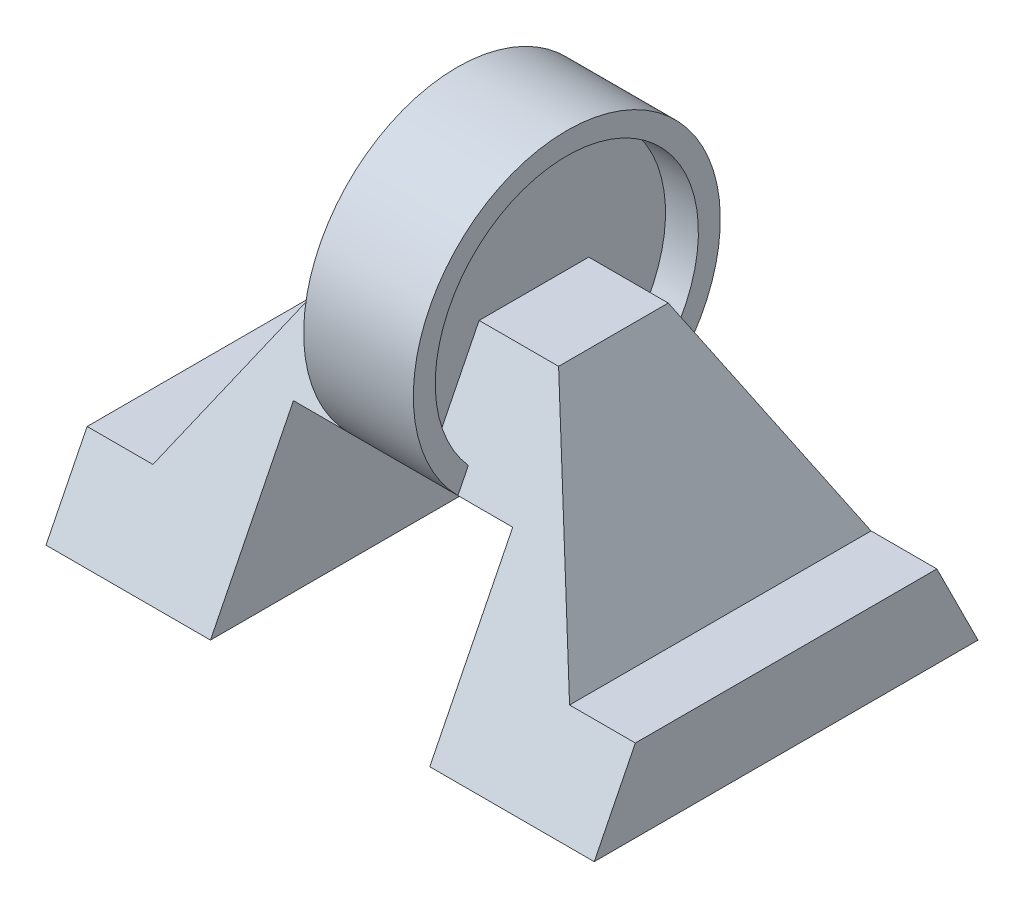
SolidWorks part; units mm, degrees
ref_plane "Front Plane" through (0, 0, 0) normal (0, 0, 1) x (1, 0, 0)
ref_plane "Top Plane" through (0, 0, 0) normal (0, 1, 0) x (1, 0, 0)
ref_plane "Right Plane" through (0, 0, 0) normal (1, 0, 0) x (0, 0, -1)
sketch "Sketch2" plane through (0, 0, 0) normal (1, 0, 0) x (0, 0, -1)
  line L0 (-35, 0) -> (35, 0)
  line L1 (35, 0) -> (10, 50)
  line L2 (10, 50) -> (-10, 50)
  line L3 (-10, 50) -> (-35, 0)
  line L4 (0, 0) -> (0, 29.4444) construction
  line L5 (-19.8659, 30.2682) -> (19.8659, 30.2682)
  arc A0 (-19.8659, 30.2682) -> (19.8659, 30.2682) centre (0, 50) cw
  arc A1 (-13.6622, 30.2682) -> (13.6622, 30.2682) centre (0, 50) cw
  point P4 (0, 0)
  point P12 (0, 0)
  point P14 (0, 0)
  dimension "D4" = 28
  dimension "D5" = 24
  dimension "D1" = 20
  dimension "D2" = 70
  dimension "D3" = 50
extrude "Boss-Extrude1" add sketch "Sketch2" along normal mid plane 100 contours L0 L4 L5 L3 | L4 L0 L1 L5 | L4 L5 A1 L1 L2 | L1 A1 L5 | L5 A1 L3 | L5 L4 L2 L3 A1 region at (0, 14.793, 26.7508) region at (0, 31.5043, 17.24) region at (0, 39.3448, 0) region at (0, 31.5043, -17.24)
extrude "Boss-Extrude2" add sketch "Sketch2<5>" along normal mid plane 20 contours L4 A1 L1 A0 | A1 L4 A0 L3 | L5 A1 L3 | L1 A1 L5 region at (0, 77.2642, 0) region at (0, 31.5043, 17.24) region at (0, 31.5043, -17.24)
sketch "Sketch2<5>" plane through (0, 0, 0) normal (1, 0, 0) x (0, 0, -1) same geometry as "Sketch2"
extrude "Boss-Extrude3" add sketch "Sketch2<6>" along normal mid plane 8 contours L4 L2 L1 A1 | L2 L4 A1 L3 region at (0, 56.6545, 0)
sketch "Sketch2<6>" plane through (0, 0, 0) normal (1, 0, 0) x (0, 0, -1) same geometry as "Sketch2"
sketch "Sketch3" plane through (0, 0, 0) normal (0, 0, 1) x (1, 0, 0)
  line L0 (0, 0) -> (0, 50000) construction
  line L1 (50, 50) -> (-50, 50) construction
  line L3 (50, 15) -> (38, 15)
  line L5 (-38, 15) -> (-18.5, 50)
  line L8 (50, 0) -> (-50, 0) construction
  line L9 (-20, 0) -> (-20, 30.2682)
  line L19 (50, 0) -> (50, 15)
  line L20 (50, 0) -> (20, 0)
  line L21 (20, 0) -> (20, 30.2682)
  line L22 (38, 15) -> (18.5, 50)
  line L23 (-20, 30.2682) -> (20, 30.2682)
  line L24 (18.5, 50) -> (-18.5, 50)
  line L25 (10, 30.2682) -> (-10, 30.2682) construction
  line L26 (-50, 50) -> (-50, 0) construction
  line L27 (-50, 0) -> (-20, 0)
  line L28 (-50, 0) -> (-50, 15)
  line L29 (-50, 15) -> (-38, 15)
  line L30 (-50, 15) -> (-50, 50)
  line L31 (-50, 50) -> (-18.5, 50)
  line L32 (-20, 0) -> (20, 0)
  line L33 (50, 15) -> (50, 50)
  line L34 (50, 50) -> (18.5, 50)
  point P4 (0, 50)
  dimension "D1" = 15
  dimension "D2" = 12
  dimension "D3" = 30
  dimension "D4" = 37
extrude "Cut-Extrude1" cut sketch "Sketch3" against normal through all both and the other way through all contours L31 L30 L29 L5 | L32 L0 L23 L9 | L0 L32 L21 L23 | L33 L34 L22 L3 region at (-10, 15.1341, 0) region at (10, 15.1341, 0) region at (38.3966, 35.1149, 0) region at (-38.3966, 35.1149, 0)
